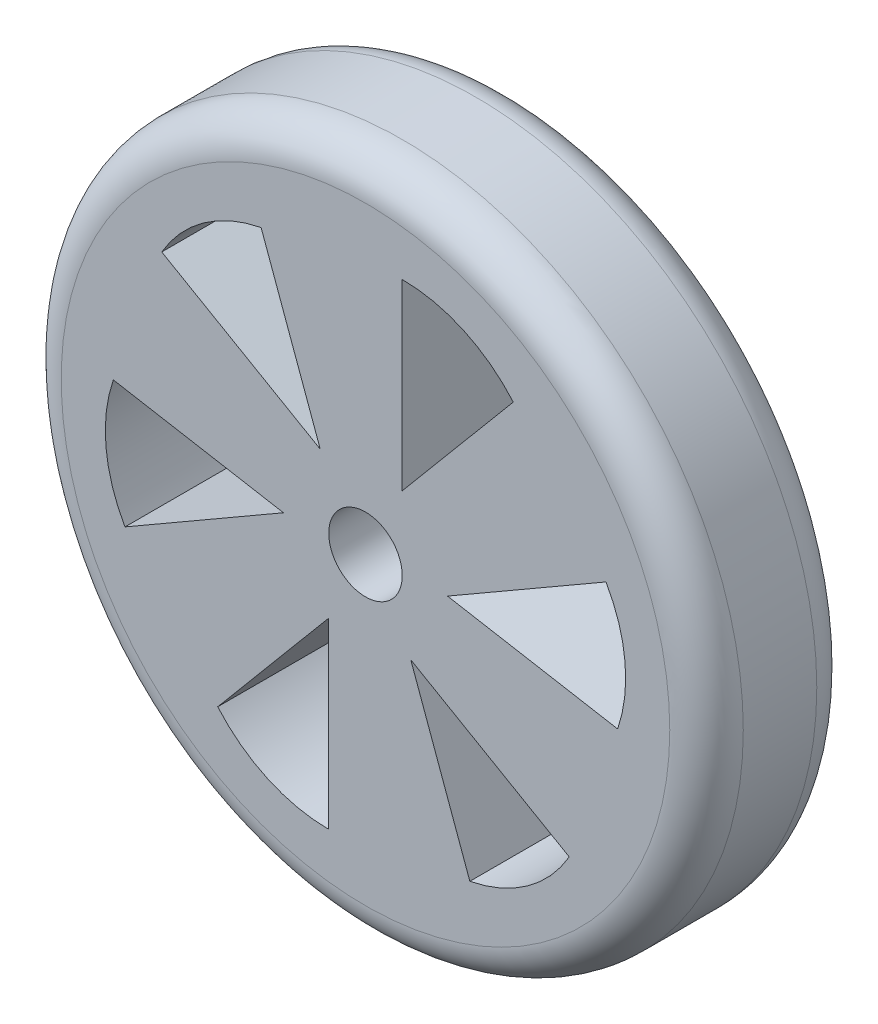
SolidWorks part; units mm, degrees
material "炭素鋼(普通)"
ref_plane "VERT" through (0, 0, 0) normal (0, 0, 1) x (1, 0, 0)
ref_plane "HOR" through (0, 0, 0) normal (0, 1, 0) x (1, 0, 0)
ref_plane "CTR" through (0, 0, 0) normal (1, 0, 0) x (0, 0, -1)
ref_axis "A_X" through (51.0346, 0, 0) along (-1, 0, 0)
ref_axis "A_Y" through (0, 51.0346, 0) along (0, -1, 0)
ref_axis "A_Z" through (0, 0, 21) along (0, 0, -1)
sketch3d "PNT_CG"
  point P0 (0, 0, 0)
sketch "Sketch1" plane through (0, 0, 0) normal (0, 0, 1) x (1, 0, 0)
  circle A0 centre (0, 0) radius 46.3951
  point P3 (0, 0)
extrude "Boss-Extrude1" add sketch "Sketch1" along normal blind 20
fillet "Fillet1" radius 5 2 edges at (46.3951, 0, 0) (46.3951, 0, 20)
sketch "Sketch2" plane through (0, 0, 20) normal (0, 0, 1) x (1, 0, 0)
  circle A0 centre (0, 0) radius 5
  dimension "D1" = 10
extrude "Cut-Extrude1" cut sketch "Sketch2" against normal through all contours A0
sketch "Sketch3" plane through (0, 0, 20) normal (0, 0, 1) x (1, 0, 0)
  line L0 (5, 10) -> (5, 34.8911)
  line L1 (20.1043, 28.0006) -> (5, 10)
  line L2 (0, -11) -> (0, 11) construction
  line L4 (11, 0) -> (-11, 0) construction
  line L5 (34.3014, -3.4105) -> (11.1603, 0.6699)
  line L6 (11.1603, 0.6699) -> (32.7165, 13.1154)
  line L7 (14.1971, -31.4111) -> (6.1603, -9.3301)
  line L8 (6.1603, -9.3301) -> (27.7165, -21.7757)
  line L9 (-20.1043, -28.0006) -> (-5, -10)
  line L10 (-5, -10) -> (-5, -34.8911)
  line L11 (-34.3014, 3.4105) -> (-11.1603, -0.6699)
  line L12 (-11.1603, -0.6699) -> (-32.7165, -13.1154)
  line L13 (-14.1971, 31.4111) -> (-6.1603, 9.3301)
  line L14 (-6.1603, 9.3301) -> (-27.7165, 21.7757)
  arc A0 (5, 34.8911) -> (20.1043, 28.0006) centre (5, 14.8911) cw
  arc A1 (32.7165, 13.1154) -> (34.3014, -3.4105) centre (15.396, 3.1154) cw
  arc A2 (27.7165, -21.7757) -> (14.1971, -31.4111) centre (10.396, -11.7757) cw
  arc A3 (-5, -34.8911) -> (-20.1043, -28.0006) centre (-5, -14.8911) cw
  arc A4 (-32.7165, -13.1154) -> (-34.3014, 3.4105) centre (-15.396, -3.1154) cw
  arc A5 (-27.7165, 21.7757) -> (-14.1971, 31.4111) centre (-10.396, 11.7757) cw
  point P30 (0, 0)
  dimension "D2" = 20
  dimension "D5" = 6
  dimension "D1" = 5
  dimension "D3" = 10
  dimension "D4" = 40
extrude "Cut-Extrude2" cut sketch "Sketch3" against normal through all contours L0 A0 L1 | L5 L6 A1 | L7 L8 A2 | L9 L10 A3 | L11 L12 A4 | L13 L14 A5
